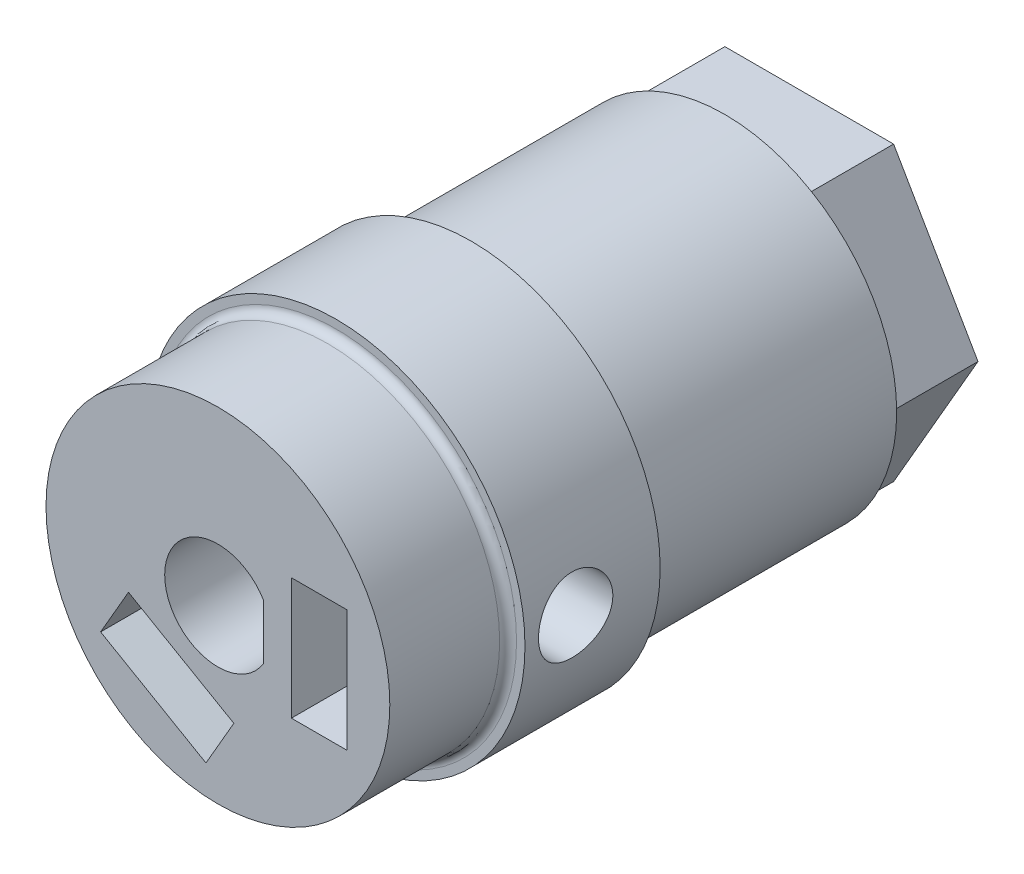
SolidWorks part; units mm, degrees
ref_plane "Спереди" through (0, 0, 0) normal (0, 0, 1) x (1, 0, 0)
ref_plane "Сверху" through (0, 0, 0) normal (0, 1, 0) x (1, 0, 0)
ref_plane "Справа" through (0, 0, 0) normal (1, 0, 0) x (0, 0, -1)
sketch "Эскиз1" plane through (0, 0, 0) normal (1, 0, 0) x (0, 0, -1)
  line L0 (0, 0) -> (0, 7.025)
  line L1 (0, 7.025) -> (7, 7.025)
  line L2 (7, 7.025) -> (7, 8.025)
  line L3 (7, 8.025) -> (15, 8.025)
  line L4 (15, 8.025) -> (15, 7.025)
  line L5 (15, 7.025) -> (30, 7.025)
  line L6 (30, 7.025) -> (30, -1.4)
  line L7 (30, -1.4) -> (14.5, -1.4)
  line L8 (0, 0) -> (14.5, 0)
  line L9 (14.5, 0) -> (14.5, -1.4)
  line L10 (0, -3.15) -> (38.6687, -3.15) construction
  line L11 (0, -3.15) -> (0, 0) construction
  line L12 (14.5, -1.4) -> (14.5, -3.15) construction
  dimension "D1" = 8
  dimension "D2" = 7
  dimension "D3" = 15
  dimension "D4" = 1
  dimension "D5" = 1.75
  dimension "D6" = 14.5
  dimension "D7" = 10.175
  dimension "D8" = 3.15
  dimension "D9" = 1.4
revolve "Повернуть1" add sketch "Эскиз1" angle 360 about L10
sketch "Эскиз2" plane through (0, 0, -30) normal (0, 0, -1) x (-1, 0, 0)
  line L1 (-7, -10.15) -> (7, -10.15) construction
  line L2 (-7, -10.15) -> (-7, 3.85) construction
  line L3 (-7, 3.85) -> (7, 3.85) construction
  line L4 (7, -10.15) -> (7, 3.85) construction
  line L5 (-7, -10.15) -> (7, 3.85) construction
  line L6 (-7, 3.85) -> (7, -10.15) construction
  line L7 (4.9941, 5.5) -> (-4.9941, 5.5)
  line L8 (-4.9941, 5.5) -> (-9.9882, -3.15)
  line L9 (-9.9882, -3.15) -> (-4.9941, -11.8)
  line L10 (-4.9941, -11.8) -> (4.9941, -11.8)
  line L11 (4.9941, -11.8) -> (9.9882, -3.15)
  line L12 (9.9882, -3.15) -> (4.9941, 5.5)
  circle A0 centre (0, -3.15) radius 1.75
  circle A1 centre (0, -3.15) radius 1.75 construction
  circle A2 centre (0, -3.15) radius 8.65 construction
  point P0 (0, -3.15)
  dimension "D1" = 14
  dimension "D2" = 17.3
extrude "Бобышка-Вытянуть1" add sketch "Эскиз2" along normal blind 5
sketch "Эскиз3" plane through (0, 0, 0) normal (0, 0, 1) x (1, 0, 0)
  line L0 (2.7, -4.7725) -> (2.7, -1.5275)
  line L1 (2.7, -3.15) -> (5.7, -3.15) construction
  line L3 (6.95, -6.85) -> (4.45, -6.85)
  line L4 (6.95, -6.85) -> (6.95, 0.55)
  line L5 (6.95, 0.55) -> (4.45, 0.55)
  line L6 (4.45, -6.85) -> (4.45, 0.55)
  line L7 (6.95, -6.85) -> (4.45, 0.55) construction
  line L8 (6.95, 0.55) -> (4.45, -6.85) construction
  circle A0 centre (0, -3.15) radius 3.15 construction
  arc A1 (2.7, -1.5275) -> (2.7, -4.7725) centre (0, -3.15) cw
  dimension "D1" = 2.7
  dimension "D2" = 2.5
  dimension "D3" = 7.4
  dimension "D4" = 3
extrude "Бобышка-Вытянуть2" add sketch "Эскиз3" against normal blind 15
sketch "Эскиз4" plane through (2.7, 0, 0) normal (-1, 0, 0) x (0, 0, 1)
  line L0 (-10, -3.15) -> (0, -3.15) construction
  line L1 (0, -1.5275) -> (0, -4.7725) construction
  circle A0 centre (-10, -3.15) radius 2.2
  point P2 (-12.2, -3.15)
  dimension "D1" = 4.4
  dimension "D2" = 10
  dimension "D3" = 12.2
extrude "Вырез-Вытянуть1" cut sketch "Эскиз4" against normal blind 12 and the other way blind 0.2
fillet "Скругление1" radius 1 1 edges at (-3.15, -3.15, -14.5)
sketch "Эскиз9" plane through (0, 0, 0) normal (0, 0, 1) x (1, 0, 0)
  line L0 (0, -3.15) -> (10.175, -3.15) construction
  line L1 (7.65, 0.45) -> (4.35, 0.45)
  line L2 (7.65, 0.45) -> (7.65, -6.75)
  line L3 (7.65, -6.75) -> (4.35, -6.75)
  line L4 (4.35, 0.45) -> (4.35, -6.75)
  line L5 (7.65, 0.45) -> (4.35, -6.75) construction
  line L6 (7.65, -6.75) -> (4.35, 0.45) construction
  line L7 (-6.9427, -7.9751) -> (-5.2927, -5.1172)
  line L8 (-0.7073, -11.5751) -> (-6.9427, -7.9751)
  line L9 (0.9427, -8.7172) -> (-5.2927, -5.1172)
  line L10 (-0.7073, -11.5751) -> (0.9427, -8.7172)
  line L11 (-6.9427, -7.9751) -> (0.9427, -8.7172) construction
  line L12 (-0.7073, -11.5751) -> (-5.2927, -5.1172) construction
  line L13 (0, -3.15) -> (-5.0875, -11.9618) construction
  circle A1 centre (0, -3.15) radius 10.175 construction
  point P0 (6, -3.15)
  point P19 (0, -3.15)
  dimension "D1" = 7.2
  dimension "D2" = 3.3
  dimension "D3" = 6
  dimension "D5" = 120
  dimension "D6" = 4.35
  dimension "D4" = 2
extrude "Вырез-Вытянуть5" cut sketch "Эскиз9" against normal blind 13
sketch "Эскиз10" plane through (4.35, 0, 0) normal (1, 0, 0) x (0, 0, -1)
  line L0 (13, 0.45) -> (0, 0.45) construction
  line L1 (5.8431, -3.15) -> (7.9215, -6.75)
  line L2 (7.9215, -6.75) -> (12.0785, -6.75)
  line L3 (12.0785, -6.75) -> (14.1569, -3.15)
  line L4 (14.1569, -3.15) -> (12.0785, 0.45)
  line L5 (12.0785, 0.45) -> (7.9215, 0.45)
  line L6 (7.9215, 0.45) -> (5.8431, -3.15)
  circle A0 centre (10, -3.15) radius 3.6 construction
extrude "Вырез-Вытянуть6" cut sketch "Эскиз10" along normal blind 3.3
sketch "Эскиз12" plane through (-3.539, -6.1297, 0) normal (-0.5, -0.866, 0) x (0.866, -0.5, 0)
  line L0 (1.575, -10) -> (1.575, 0) construction
  line L1 (5.175, 0) -> (-2.025, 0) construction
  circle A0 centre (1.575, -10) radius 2.2
  dimension "D1" = 10
  dimension "D2" = 4.4
extrude "Вырез-Вытянуть7" cut sketch "Эскиз12" against normal blind 5 and the other way blind 10
sketch "Эскиз13" plane through (-3.539, -6.1297, 0) normal (-0.5, -0.866, 0) x (0.866, -0.5, 0)
  line L0 (-2.025, -13) -> (-2.025, 0) construction
  line L1 (-2.025, -7.9215) -> (-2.025, -12.0785)
  line L2 (-2.025, -12.0785) -> (1.575, -14.1569)
  line L3 (1.575, -14.1569) -> (5.175, -12.0785)
  line L4 (5.175, -12.0785) -> (5.175, -7.9215)
  line L5 (5.175, -7.9215) -> (1.575, -5.8431)
  line L6 (1.575, -5.8431) -> (-2.025, -7.9215)
  circle A0 centre (1.575, -10) radius 3.6 construction
  circle A1 centre (1.575, -10) radius 2.2 construction
extrude "Вырез-Вытянуть8" cut sketch "Эскиз13" along normal blind 3.4
fillet "Скругление2" radius 0.5 1 edges at (10.175, -3.15, -7)
